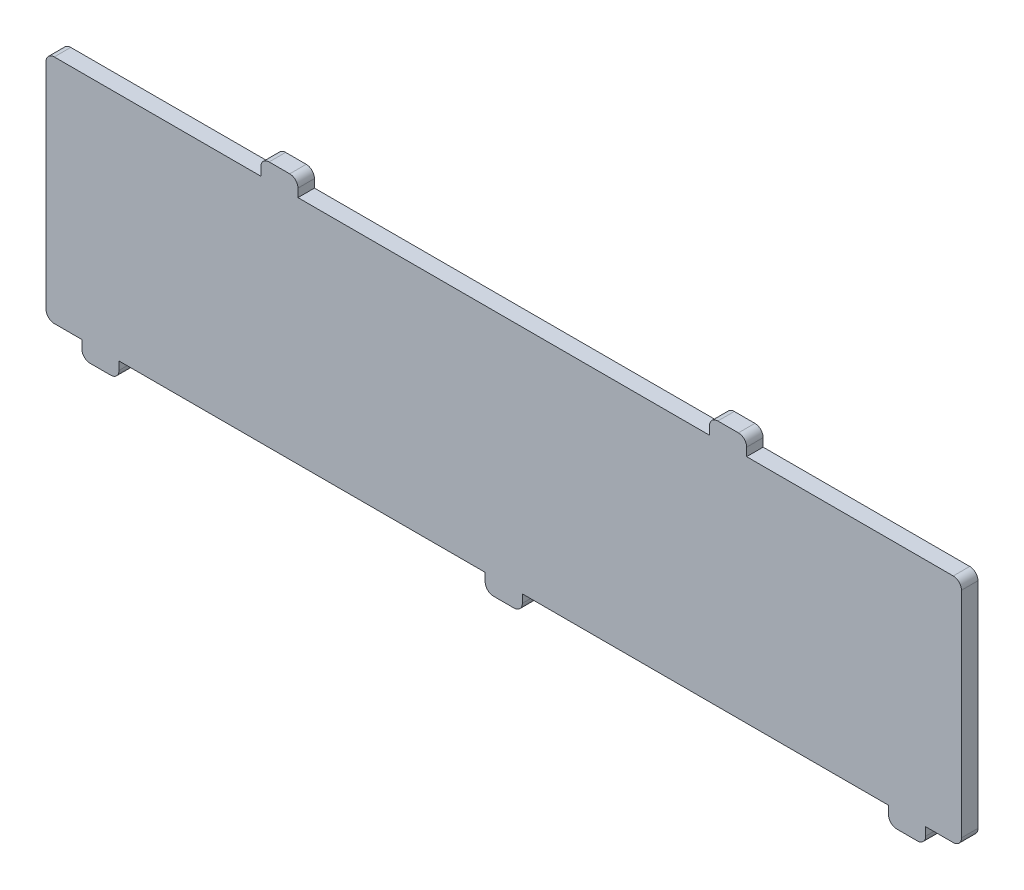
SolidWorks part; units mm, degrees
ref_plane "前基準面" through (0, 0, 0) normal (0, 0, 1) x (1, 0, 0)
ref_plane "上基準面" through (0, 0, 0) normal (0, 1, 0) x (1, 0, 0)
ref_plane "右基準面" through (0, 0, 0) normal (1, 0, 0) x (0, 0, -1)
sketch "Sketch1" plane through (0, 0, 0) normal (0, 0, 1) x (1, 0, 0)
  line L0 (0, 0) -> (0, -31.2064) construction
  line L1 (-55.5, 14) -> (55.5, 14)
  line L2 (-55.5, 14) -> (-55.5, -14)
  line L3 (-55.5, -14) -> (55.5, -14)
  line L4 (55.5, 14) -> (55.5, -14)
  line L5 (-55.5, 14) -> (55.5, -14) construction
  line L6 (-55.5, -14) -> (55.5, 14) construction
  line L7 (0, -31.2064) -> (0, 29.4941) construction
  line L8 (-2.25, -14) -> (2.25, -16) construction
  line L9 (-2.25, -14) -> (2.25, -14)
  line L10 (-2.25, -14) -> (-2.25, -16)
  line L11 (-2.25, -16) -> (2.25, -16)
  line L12 (2.25, -14) -> (2.25, -16)
  line L13 (-2.25, -16) -> (2.25, -14) construction
  line L14 (-51.15, -14) -> (-46.65, -16) construction
  line L15 (-51.15, -14) -> (-46.65, -14)
  line L16 (-51.15, -14) -> (-51.15, -16)
  line L17 (-51.15, -16) -> (-46.65, -16)
  line L18 (-46.65, -14) -> (-46.65, -16)
  line L19 (-46.65, -14) -> (-51.15, -16) construction
  line L20 (51.15, -16) -> (46.65, -16)
  line L21 (46.65, -14) -> (46.65, -16)
  line L22 (51.15, -14) -> (46.65, -14)
  line L23 (51.15, -14) -> (51.15, -16)
  line L24 (-48.9, -15) -> (-48.9, 18.4346) construction
  line L25 (0, -15.6032) -> (0, 17.9346) construction
  line L26 (46.65, -14) -> (51.15, -16) construction
  line L27 (51.15, -14) -> (46.65, -16) construction
  line L28 (-29.45, 16) -> (-24.95, 14) construction
  line L29 (-29.45, 14) -> (-24.95, 14)
  line L30 (-29.45, 14) -> (-29.45, 16)
  line L31 (-29.45, 16) -> (-24.95, 16)
  line L32 (-24.95, 14) -> (-24.95, 16)
  line L33 (-24.95, 16) -> (-29.45, 14) construction
  line L34 (29.45, 16) -> (24.95, 16)
  line L35 (24.95, 14) -> (24.95, 16)
  line L36 (29.45, 14) -> (24.95, 14)
  line L37 (29.45, 14) -> (29.45, 16)
  point P0 (0, 0)
  point P13 (0, -15)
  point P32 (-27.2, 15)
  dimension "D1" = 28
  dimension "D2" = 111
  dimension "D3" = 2
  dimension "D4" = 4.5
  dimension "D5" = 2
  dimension "D6" = 4.5
  dimension "D7" = 6.6
  dimension "D8" = 2
  dimension "D9" = 4.5
  dimension "D10" = 27.2
extrude "Boss-Extrude1" add sketch "Sketch1" along normal mid plane 2 contours L4 L1 L2 L3 | L12 L3 L10 L11 | L1 L37 L34 L35 | L1 L32 L31 L30 | L18 L17 L16 L15 | L23 L20 L21 L22 region at (0, 0, 0) region at (-27.2, 15, 0) region at (27.2, 15, 0) region at (0, -15, 0)
fillet "Fillet1" radius 1 14 edges at (-55.5, 14, 0) (-55.5, -14, 0) (-46.65, -16, 0) (-51.15, -16, 0) (2.25, -16, 0) (-2.25, -16, 0) (46.65, -16, 0) (51.15, -16, 0) (55.5, -14, 0) (55.5, 14, 0) (29.45, 16, 0) (24.95, 16, 0) (-24.95, 16, 0) (-29.45, 16, 0)
